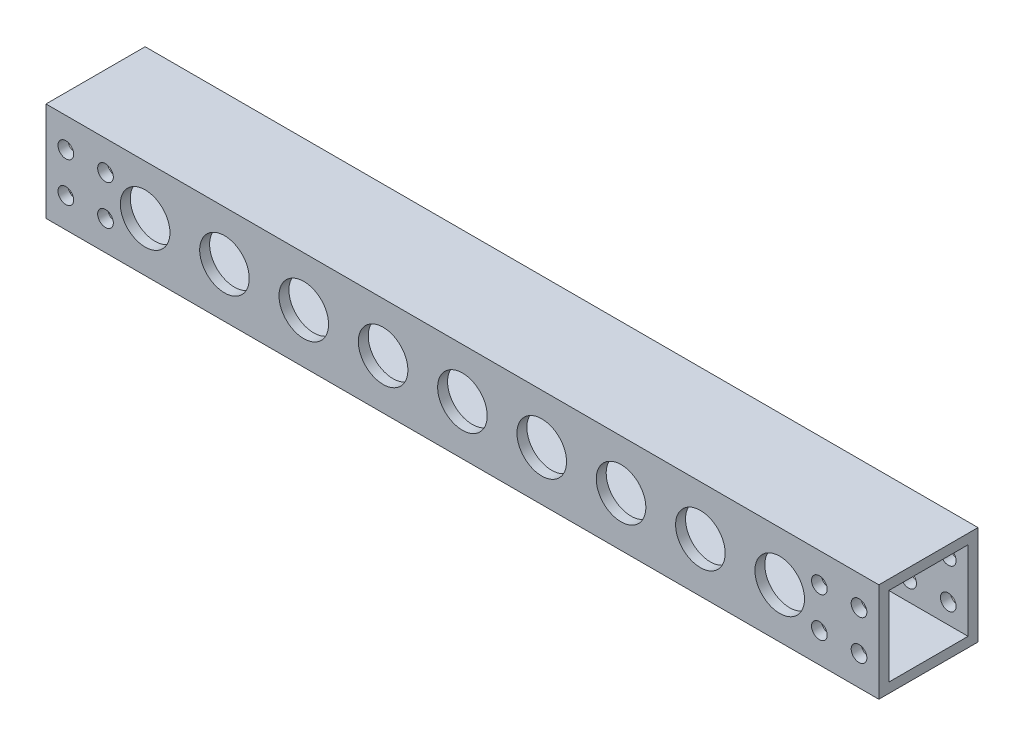
SolidWorks part; units mm, degrees
material "6061-T6 (SS)"
ref_plane "Front Plane" through (0, 0, 0) normal (0, 0, 1) x (1, 0, 0)
ref_plane "Top Plane" through (0, 0, 0) normal (0, 1, 0) x (1, 0, 0)
ref_plane "Right Plane" through (0, 0, 0) normal (1, 0, 0) x (0, 0, -1)
sketch "Sketch1" plane through (0, 0, 0) normal (0, 0, 1) x (1, 0, 0)
  line L1 (0, 0) -> (-266.7, 0)
  line L2 (0, 0) -> (0, -31.75)
  line L3 (0, -31.75) -> (-266.7, -31.75)
  line L4 (-266.7, 0) -> (-266.7, -31.75)
  dimension "D1" = 266.7
  dimension "D2" = 31.75
extrude "Boss-Extrude1" add sketch "Sketch1" along normal blind 31.75
sketch "Sketch2" plane through (0, 0, 31.75) normal (0, 0, 1) x (1, 0, 0)
  line L0 (-266.7, -31.75) -> (0, -31.75) construction
  line L1 (-266.7, 0) -> (-266.7, -31.75) construction
  circle A0 centre (-234.95, -15.875) radius 7.9375
  dimension "D1" = 15.875
  dimension "D3" = 15.875
  dimension "D2" = 31.75
extrude "Cut-Extrude1" cut sketch "Sketch2" against normal blind 31.75
pattern_linear "LPattern1" count 9 spacing 25.4 along (1, 0, 0) of "Cut-Extrude1"
sketch "Sketch3" plane through (0, 0, 31.75) normal (0, 0, 1) x (1, 0, 0)
  line L0 (-266.7, -31.75) -> (0, -31.75) construction
  line L1 (-266.7, 0) -> (-266.7, -31.75) construction
  circle A0 centre (-260.35, -9.525) radius 2.5082
  circle A1 centre (-247.65, -9.525) radius 2.5082
  circle A2 centre (-260.35, -22.225) radius 2.5082
  circle A3 centre (-247.65, -22.225) radius 2.5082
  point P8 (-254, -15.875)
  dimension "D1" = 5.0165
  dimension "D2" = 15.875
  dimension "D3" = 12.7
  dimension "D4" = 6.35
  dimension "D5" = 6.35
  dimension "D6" = 6.35
  dimension "D7" = 6.35
  dimension "D8" = 6.35
  dimension "D9" = 6.35
  dimension "D10" = 6.35
  dimension "D11" = 6.35
extrude "Cut-Extrude2" cut sketch "Sketch3" against normal blind 31.75
sketch "Sketch4" plane through (0, 0, 0) normal (1, 0, 0) x (0, 0, -1)
  line L0 (-31.75, -31.75) -> (-31.75, 0) construction
  line L1 (-28.575, -3.175) -> (-3.175, -3.175)
  line L2 (-28.575, -3.175) -> (-28.575, -28.575)
  line L3 (-28.575, -28.575) -> (-3.175, -28.575)
  line L4 (-3.175, -3.175) -> (-3.175, -28.575)
  line L5 (-31.75, -31.75) -> (0, -31.75) construction
  dimension "D1" = 25.4
  dimension "D2" = 25.4
  dimension "D3" = 3.175
  dimension "D4" = 3.175
extrude "Cut-Extrude3" cut sketch "Sketch4" against normal blind 266.7
ref_plane "Plane1" through (-133.35, 0, 0) normal (1, 0, 0) x (0, 0, -1)
mirror "Mirror1" about plane through (-133.35, 0, 0) normal (1, 0, 0) of "Cut-Extrude2"
